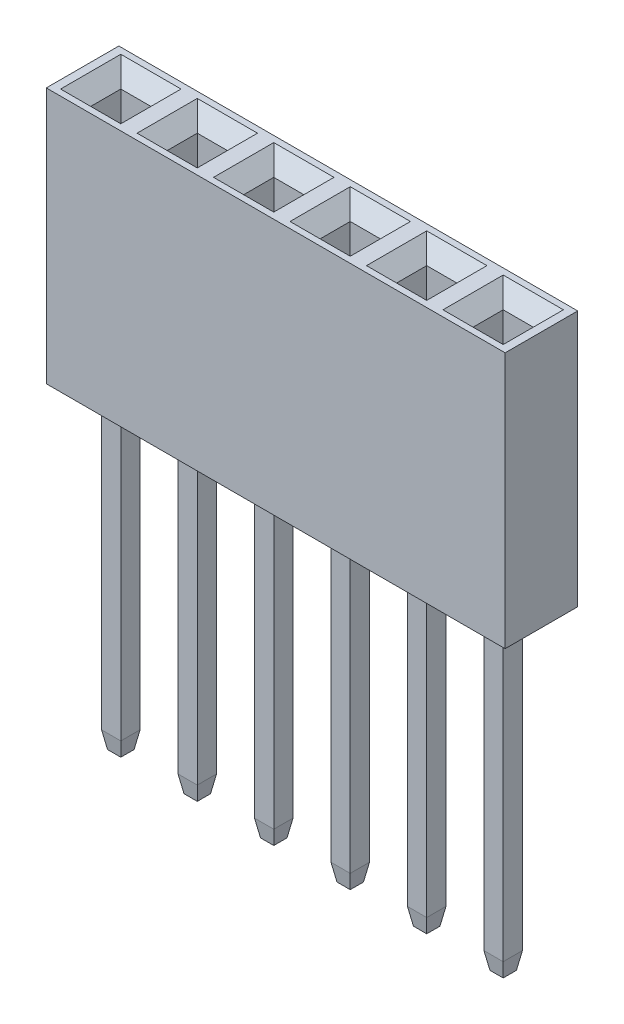
SolidWorks part; units mm, degrees
material "PA Type 6"
ref_plane "Front Plane" through (0, 0, 0) normal (0, 0, 1) x (1, 0, 0)
ref_plane "Top Plane" through (0, 0, 0) normal (0, 1, 0) x (1, 0, 0)
ref_plane "Right Plane" through (0, 0, 0) normal (1, 0, 0) x (0, 0, -1)
ref_plane "Plane1" through (0, -1.65, 0) normal (0, 1, 0) x (1, 0, 0)
sketch "Sketch2" plane through (0, 0, 0) normal (0, 1, 0) x (1, 0, 0)
  line L0 (0, -55) -> (0, 55) construction
  line L1 (-1.27, 1.205) -> (13.97, 1.205)
  line L2 (-1.27, 1.205) -> (-1.27, -1.205)
  line L3 (-1.27, -1.205) -> (13.97, -1.205)
  line L4 (13.97, 1.205) -> (13.97, -1.205)
  line L5 (-55, 0) -> (55, 0) construction
  dimension "D1" = 15.24
  dimension "D2" = 1.27
  dimension "D3" = 2.41
  dimension "D4" = 1.205
extrude "Boss-Extrude1" add sketch "Sketch2" along normal blind 8.51
sketch "Sketch5" plane through (0, 8.51, 0) normal (0, 1, 0) x (1, 0, 0)
  line L0 (-55, 0) -> (55, 0) construction
  line L1 (0.5, 0.5) -> (-0.5, 0.5)
  line L2 (0.5, 0.5) -> (0.5, -0.5)
  line L3 (0.5, -0.5) -> (-0.5, -0.5)
  line L4 (-0.5, 0.5) -> (-0.5, -0.5)
  line L5 (0, -55) -> (0, 55) construction
  dimension "D1" = 0.5
  dimension "D2" = 1
  dimension "D3" = 0.5
extrude "Cut-Extrude1" cut sketch "Sketch5" against normal blind 5
chamfer "Chamfer1" distance 0.5 angle 45 4 edges at (-0.5, 8.51, 0) (0, 8.51, 0.5) (0.5, 8.51, 0) (0, 8.51, -0.5)
pattern_linear "LPattern3" count 6 spacing 2.54 along (1, 0, 0) of "Chamfer1", "Cut-Extrude1"
ref_axis "Axis1" through (0, -11.44, 0) along (0, 1, 0)
sketch "Sketch11" plane through (0, 0, 0) normal (0, -1, 0) x (1, 0, 0)
  line L0 (0, 0) -> (2.54, 0) construction
  line L1 (-0.32, 0.32) -> (0.32, 0.32)
  line L2 (-0.32, 0.32) -> (-0.32, -0.32)
  line L3 (-0.32, -0.32) -> (0.32, -0.32)
  line L4 (0.32, 0.32) -> (0.32, -0.32)
  line L5 (-0.32, 0.32) -> (0.32, -0.32) construction
  line L6 (-0.32, -0.32) -> (0.32, 0.32) construction
  point P0 (0, 0)
  dimension "0.64" = 0.64
sketch "Sketch12" plane through (0, 0, 0) normal (0, 0, 1) x (1, 0, 0)
  line L0 (0, 8.51) -> (0, -10.49) construction
  line L1 (-1.27, 8.51) -> (13.97, 8.51) construction
  dimension "D1" = 19
extrude "Boss-Extrude2" add sketch "Sketch11" along normal blind 9.92
sketch "Sketch13" plane through (0, -9.92, 0) normal (0, -1, 0) x (1, 0, 0)
  line L4 (0.32, -0.32) -> (0.32, 0.32)
  line L5 (0.32, 0.32) -> (-0.32, 0.32)
  line L6 (-0.32, 0.32) -> (-0.32, -0.32)
  line L7 (-0.32, -0.32) -> (0.32, -0.32)
  line L8 (0.32, -0.32) -> (0.32, 0.32)
  line L9 (0.32, 0.32) -> (-0.32, 0.32)
  line L10 (-0.32, 0.32) -> (-0.32, -0.32)
  line L11 (-0.32, -0.32) -> (0.32, -0.32)
  dimension "D1" = 0
ref_plane "Plane2" through (0, -10.49, 0) normal (0, -1, 0) x (-1, 0, 0)
sketch "Sketch14" plane through (0, -10.49, 0) normal (0, -1, 0) x (-1, 0, 0)
  line L1 (-0.22, 0.22) -> (0.22, 0.22)
  line L2 (-0.22, 0.22) -> (-0.22, -0.22)
  line L3 (-0.22, -0.22) -> (0.22, -0.22)
  line L4 (0.22, 0.22) -> (0.22, -0.22)
  line L5 (-0.22, 0.22) -> (0.22, -0.22) construction
  line L6 (-0.22, -0.22) -> (0.22, 0.22) construction
  point P0 (0, 0)
  dimension "D1" = 0.44
loft "Loft1" add profiles "Sketch13", "Sketch14" connector at (-0.32, -9.92, 0.32) connector at (-0.22, -10.49, 0.22)
pattern_linear "LPattern4" count 6 spacing 2.54 along (1, 0, 0) of "Boss-Extrude2", "Loft1"
equation "\"D1@Sketch2\"=2.54 * 6"
